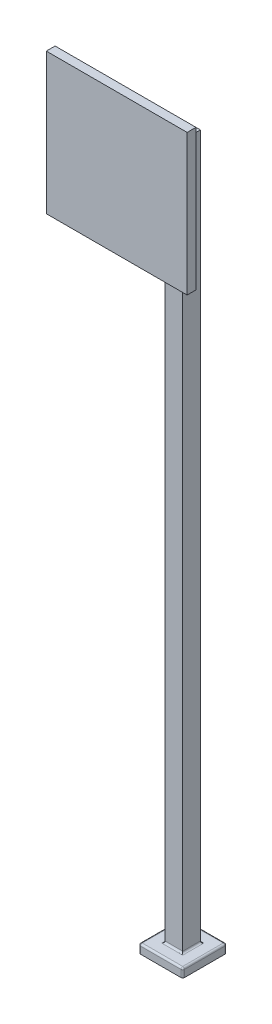
SolidWorks part; units mm, degrees
ref_plane "Front Plane" through (0, 0, 0) normal (0, 0, 1) x (1, 0, 0)
ref_plane "Top Plane" through (0, 0, 0) normal (0, 1, 0) x (1, 0, 0)
ref_plane "Right Plane" through (0, 0, 0) normal (1, 0, 0) x (0, 0, -1)
sketch "Sketch1" plane through (0, 0, 0) normal (0, 0, 1) x (1, 0, 0)
  line L1 (-50, 4000) -> (50, 4000)
  line L2 (-50, 4000) -> (-50, 0)
  line L3 (-50, 0) -> (50, 0)
  line L4 (50, 4000) -> (50, 0)
  point P4 (0, 0)
  dimension "D1" = 4000
  dimension "D2" = 100
extrude "Boss-Extrude1" add sketch "Sketch1" along normal mid plane 100
sketch "Sketch2" plane through (0, 0, 0) normal (0, 1, 0) x (1, 0, 0)
  line L1 (-125, 125) -> (125, 125)
  line L2 (-125, 125) -> (-125, -125)
  line L3 (-125, -125) -> (125, -125)
  line L4 (125, 125) -> (125, -125)
  line L5 (-125, 125) -> (125, -125) construction
  line L6 (-125, -125) -> (125, 125) construction
  point P0 (0, 0)
  dimension "D1" = 250
extrude "Boss-Extrude2" add sketch "Sketch2" against normal blind 50
sketch "Sketch3" plane through (0, 0, 0) normal (1, 0, 0) x (0, 0, -1)
  line L1 (50, 4000) -> (-350, 4000)
  line L2 (50, 4000) -> (50, 3950)
  line L3 (50, 3950) -> (-350, 3950)
  line L4 (-350, 4000) -> (-350, 3950)
  dimension "D1" = 50
  dimension "D2" = 400
extrude "Boss-Extrude3" add sketch "Sketch3" against normal mid plane 50
sketch "Sketch4" plane through (0, 0, 350) normal (0, 0, 1) x (1, 0, 0)
  line L0 (25, 4000) -> (25, 3950) construction
  line L1 (-400, 4375) -> (400, 4375)
  line L2 (-400, 4375) -> (-400, 3575)
  line L3 (-400, 3575) -> (400, 3575)
  line L4 (400, 4375) -> (400, 3575)
  line L5 (-400, 4375) -> (400, 3575) construction
  line L6 (-400, 3575) -> (400, 4375) construction
  line L7 (-25, 4000) -> (25, 4000) construction
  point P0 (0, 3975)
  point P8 (25, 3975)
  point P11 (0, 4000)
  dimension "D1" = 800
extrude "Boss-Extrude4" add sketch "Sketch4" along normal mid plane 50
fillet "Fillet1" radius 10 12 edges at (0, 0, -125) (-125, 0, 0) (0, 0, 125) (125, -25, -125) (-125, -25, -125) (-125, -25, 125) (0, 0, -50) (0, 0, 50) (50, 0, 0) (-50, 0, 0) (125, 0, 0) (125, -25, 125)
fillet "Fillet3" radius 10 4 edges at (-25, 3975, 50) (-25, 3975, 325) (25, 3975, 325) (25, 3975, 50)
fillet "Fillet4" radius 10 2 edges at (0, 3950, 325) (0, 4000, 325)
